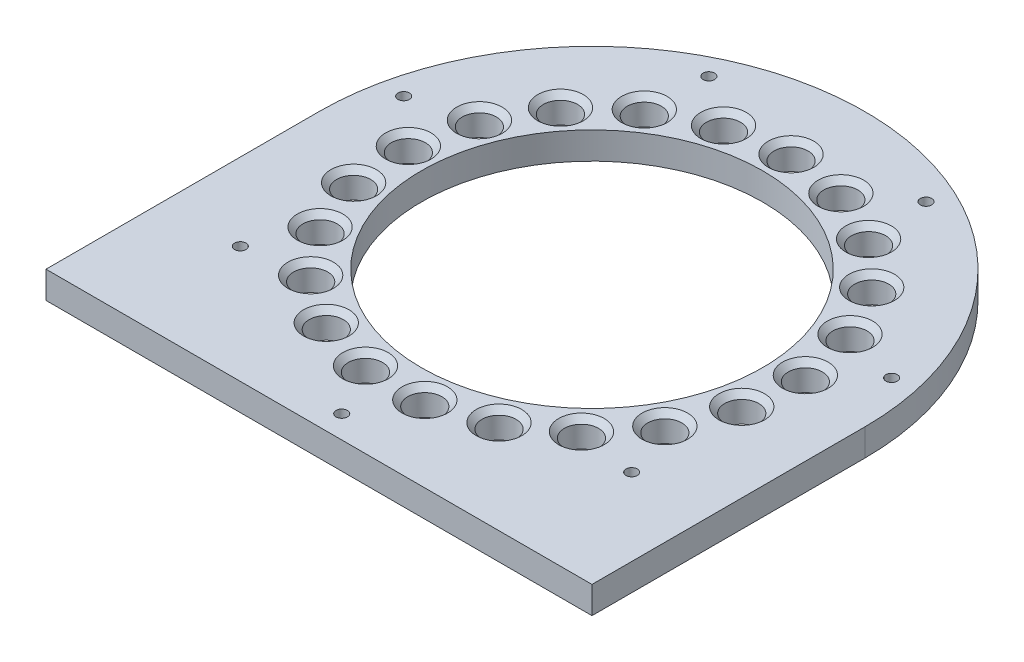
SolidWorks part; units mm, degrees
ref_plane "Front Plane" through (0, 0, 0) normal (0, 0, 1) x (1, 0, 0)
ref_plane "Top Plane" through (0, 0, 0) normal (0, 1, 0) x (1, 0, 0)
ref_plane "Right Plane" through (0, 0, 0) normal (1, 0, 0) x (0, 0, -1)
ref_axis "X Axis" through (-88.99, 0, 0) along (1, 0, 0)
ref_axis "Y Axiz" through (0, 0, 55) along (0, 0, -1)
ref_axis "Z Axis" through (0, 55, 0) along (0, -1, 0)
sketch "Sketch15" plane through (0, 0, 0) normal (0, 1, 0) x (1, 0, 0)
  line L0 (-48, 0) -> (48, 0)
  line L1 (-52.8, 0) -> (52.8, 0) construction
  line L3 (0, -26.4) -> (0, 26.4) construction
  line L4 (0, 48) -> (35.3, 48)
  line L5 (48, 32.5255) -> (48, 0)
  line L6 (0, 48) -> (-35.3, 48)
  line L7 (-48, 32.5255) -> (-48, 0)
  line L8 (-48, 32.5255) -> (-35.3, 32.5255)
  line L9 (-35.3, 32.5255) -> (-35.3, 48)
  line L10 (35.3, 48) -> (35.3, 32.5255)
  line L11 (35.3, 32.5255) -> (48, 32.5255)
  dimension "D1" = 12.7
  dimension "D2" = 32.5255
  dimension "D3" = 15.4745
  dimension "D4" = 70.6
sketch "Sketch17" plane through (0, 0, 0) normal (0, 1, 0) x (1, 0, 0)
  line L0 (-48, 0) -> (-48, -48)
  line L1 (-48, -48) -> (48, -48)
  line L2 (48, -48) -> (48, 0)
  line L3 (-48, 0) -> (48, 0)
  dimension "D1" = 48
sketch "Sketch2" plane through (0, 0, 0) normal (0, 1, 0) x (1, 0, 0)
  line L0 (0, 0) -> (0, 35) construction
  line L1 (0, 0) -> (0, -44) construction
  circle A0 centre (0, 0) radius 48
  circle A1 centre (0, 35) radius 3
  circle A2 centre (10.3164, 33.445) radius 3
  circle A3 centre (19.7162, 28.9184) radius 3
  circle A4 centre (27.3641, 21.8221) radius 3
  circle A5 centre (32.5806, 12.7869) radius 3
  circle A6 centre (34.9021, 2.6156) radius 3
  circle A7 centre (34.1225, -7.7882) radius 3
  circle A8 centre (30.3109, -17.5) radius 3
  circle A9 centre (23.806, -25.6568) radius 3
  circle A10 centre (15.1859, -31.5339) radius 3
  circle A11 centre (5.2165, -34.6091) radius 3
  circle A12 centre (-5.2165, -34.6091) radius 3
  circle A13 centre (-15.1859, -31.5339) radius 3
  circle A14 centre (-23.806, -25.6568) radius 3
  circle A15 centre (-30.3109, -17.5) radius 3
  circle A16 centre (-34.1225, -7.7882) radius 3
  circle A24 centre (0, 0) radius 35 construction
  circle A27 centre (0, -44) radius 1
  circle A28 centre (-34.4006, -27.4336) radius 1
  circle A29 centre (-42.8968, 9.7909) radius 1
  circle A30 centre (-19.0909, 39.6426) radius 1
  circle A31 centre (19.0909, 39.6426) radius 1
  circle A32 centre (42.8968, 9.7909) radius 1
  circle A33 centre (34.4006, -27.4336) radius 1
  circle A35 centre (-34.9021, 2.6156) radius 3
  circle A36 centre (-32.5806, 12.7869) radius 3
  circle A37 centre (-27.3641, 21.8221) radius 3
  circle A38 centre (-19.7162, 28.9184) radius 3
  circle A39 centre (-10.3164, 33.445) radius 3
  circle A40 centre (0, 0) radius 44 construction
  circle A42 centre (0, 35) radius 5 construction
  circle A43 centre (0, 0) radius 40 construction
  circle A45 centre (0, 0) radius 30
  point P38 (0, 0)
  point P51 (0, 0)
  point P54 (0, 0)
  point P59 (0, 0)
  dimension "D1" = 6
  dimension "D3" = 96
  dimension "D6" = 7
  dimension "D7" = 35
  dimension "D4" = 44
  dimension "D5" = 2
  dimension "D8" = 10
  dimension "60" = 60
  dimension "D2" = 21
extrude "Boss-Extrude1" add sketch "Sketch17" along normal blind 4.7625
extrude "Boss-Extrude2" add sketch "Sketch2" along normal blind 4.7625
extrude "Cut-Extrude1" cut sketch "Sketch2<11>" along normal blind 4.7625 contours A16 | A15 | A14 | A13 | A12 | A11 | A10 | A9 | A8 | A7 | A6 | A35 | A45 | A28 | A27 | A33
sketch "Sketch2<11>" plane through (0, 0, 0) normal (0, 1, 0) x (1, 0, 0) same geometry as "Sketch2"
chamfer "Chamfer1" distance 1 angle 45 21 edges at (-5.2165, 4.7625, 37.6091) (-15.1859, 4.7625, 34.5339) (-23.806, 4.7625, 28.6568) (-30.3109, 4.7625, 20.5) (-34.1225, 4.7625, 10.7882) (-34.9021, 4.7625, 0.3844) (-32.5806, 4.7625, -9.7869) (-27.3641, 4.7625, -18.8221) (-19.7162, 4.7625, -25.9184) (-10.3164, 4.7625, -30.445) (0, 4.7625, -32) (10.3164, 4.7625, -30.445) (19.7162, 4.7625, -25.9184) (27.3641, 4.7625, -18.8221) (32.5806, 4.7625, -9.7869) (34.9021, 4.7625, 0.3844) (34.1225, 4.7625, 10.7882) (30.3109, 4.7625, 20.5) (23.806, 4.7625, 28.6568) (15.1859, 4.7625, 34.5339) (5.2165, 4.7625, 37.6091)
